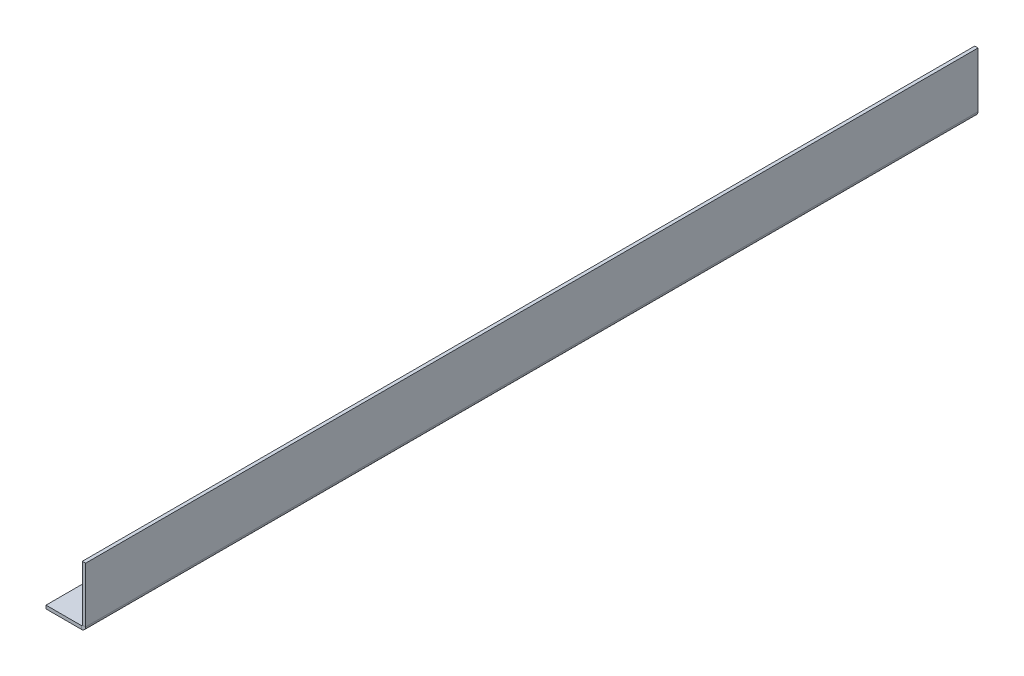
SolidWorks part; units mm, degrees
note: The reader was unsure of these and kept them because the rebuilt part matched: flange length of "Edge-Flange1".
material "Galvanized Steel"
ref_plane "Front Plane" through (0, 0, 0) normal (0, 0, 1) x (1, 0, 0)
ref_plane "Top Plane" through (0, 0, 0) normal (0, 1, 0) x (1, 0, 0)
ref_plane "Right Plane" through (0, 0, 0) normal (1, 0, 0) x (0, 0, -1)
sketch "Sketch1" plane through (0, 0, 0) normal (1, 0, 0) x (0, 0, -1)
  line L1 (0, 0) -> (675, 0)
  line L2 (0, 0) -> (0, 45)
  line L3 (0, 45) -> (675, 45)
  line L4 (675, 0) -> (675, 45)
  line L5 (0, 0) -> (675, 45) construction
  line L6 (0, 45) -> (675, 0) construction
  point P4 (337.5, 22.5)
  dimension "D1" = 675
  dimension "D2" = 45
base flange "Base-Flange1" sketch "Sketch1" thickness 2.5 reverse thickness direction no parameters "D1"=0.7366
edge flange "Edge-Flange1" sketch "Sketch8" flange angle 90 flange length 30 flange position material inside bend radius 0.7366 thickness 2.5 relief rectangular parameters "D6"=10
sketch "Sketch8" plane through (-2.5, 0, 0) normal (0, 1, 0) x (0, 0, -1)
  line L2 (0, 0) -> (0, 27.5)
  line L3 (0, 27.5) -> (675, 27.5)
  line L4 (675, 27.5) -> (675, 0)
  line L5 (675, 0) -> (0, 0) construction
  line L6 (675, 0) -> (0, 0)
bend "EdgeBend1" bend radius 0.7366 bend angle 90 parameters "D5"=1
sketch "Sketch9" plane through (0, 0, 0) normal (0, -1, 0) x (-1, 0, 0)
  line L0 (30, 675) -> (30, 0) construction
  line L1 (3.2366, 675) -> (30, 675) construction
  circle A0 centre (15, 637.5) radius 5
  dimension "D1" = 10
  dimension "D2" = 15
  dimension "D3" = 37.5
extrude "Cut-Extrude1" cut sketch "Sketch9" against normal blind 10 normal cut yes
pattern_linear "LPattern1" count 4 spacing 200 along (0, 0, 1) of "Cut-Extrude1"
sketch "Bend-Lines1" [suppressed] plane through (0, 0, 0) normal (0, 1, 0) x (1, 0, 0)
sketch "Bounding-Box1" [suppressed] plane through (0, 0, 0) normal (0, 1, 0) x (1, 0, 0)
sheet metal parameters "Sheet-Metal1" thickness 2.5 parameters "D1"=0.7366
flat pattern "Flat-Pattern1" [suppressed]
sketch "Bend-Lines2" plane through (0, 0, 0) normal (0, 1, 0) x (1, 0, 0)
sketch3d "Bounding-Box2" [suppressed]
  line L0 (-675, 0, 0) -> (0, 0, 0) construction
  line L1 (-675, 40, 0) -> (0, 40, 0) construction
  line L2 (-675, 0, 0) -> (-675, 40, 0) construction
  line L3 (0, 0, 0) -> (0, 40, 0) construction
sheet metal parameters "Sheet-Metal2" thickness 2.5 parameters "D1"=0.7366
flat pattern "Flat-Pattern1"
sketch "Bend-Lines2" plane through (0, 0, 0) normal (1, 0, 0) x (0, 0, -1)
  line L0 (0, 1.6763) -> (675, 1.6763) construction
  line L1 (0, 1.6763) -> (675, 1.6763) construction
sketch3d "Bounding-Box2" [suppressed]
  line L0 (675, -26.6473, 0) -> (0, -26.6473, 0) construction
  line L1 (675, 45, 0) -> (0, 45, 0) construction
  line L2 (675, -26.6473, 0) -> (675, 45, 0) construction
  line L3 (0, -26.6473, 0) -> (0, 45, 0) construction
bend of the flat pattern "Flatten-<EdgeBend1>1"
sheet metal parameters "Sheet-Metal3" thickness 2.5 parameters "D1"=0.7366
flat pattern "Flat-Pattern1"
sketch "Bend-Lines2" plane through (0, 0, 0) normal (1, 0, 0) x (0, 0, -1)
  line L0 (0, 1.6763) -> (675, 1.6763) construction
  line L1 (0, 1.6763) -> (675, 1.6763) construction
sketch3d "Bounding-Box2" [suppressed]
  line L0 (675, -26.6473, 0) -> (0, -26.6473, 0) construction
  line L1 (675, 45, 0) -> (0, 45, 0) construction
  line L2 (675, -26.6473, 0) -> (675, 45, 0) construction
  line L3 (0, -26.6473, 0) -> (0, 45, 0) construction
bend of the flat pattern "Flatten-<EdgeBend1>1"
sheet metal parameters "Sheet-Metal4" thickness 2.5 parameters "D1"=0.7366
flat pattern "Flat-Pattern1"
sketch "Bend-Lines2" plane through (0, 0, 0) normal (1, 0, 0) x (0, 0, -1)
  line L0 (0, 1.6763) -> (675, 1.6763) construction
  line L1 (0, 1.6763) -> (675, 1.6763) construction
sketch3d "Bounding-Box2" [suppressed]
  line L0 (675, -26.6473, 0) -> (0, -26.6473, 0) construction
  line L1 (675, 45, 0) -> (0, 45, 0) construction
  line L2 (675, -26.6473, 0) -> (675, 45, 0) construction
  line L3 (0, -26.6473, 0) -> (0, 45, 0) construction
bend of the flat pattern "Flatten-<EdgeBend1>1"
